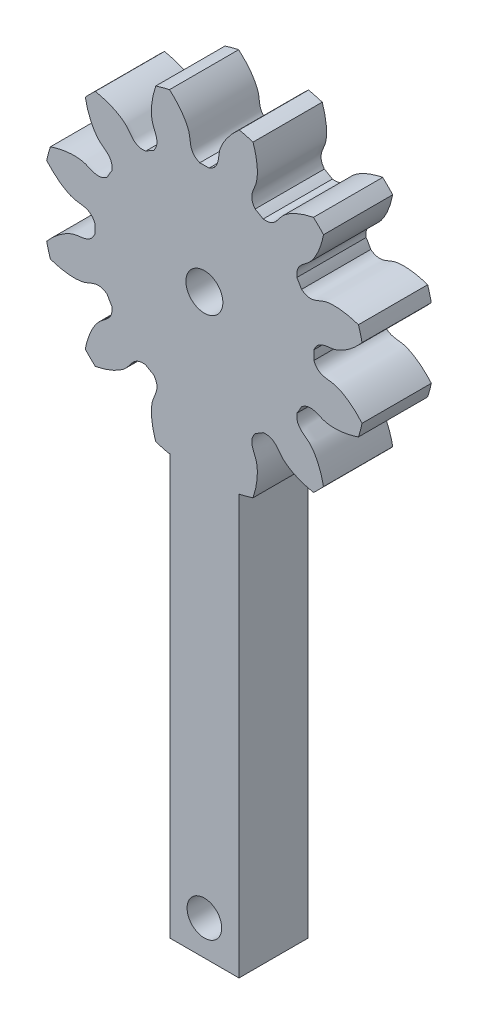
SolidWorks part; units mm, degrees
ref_plane "前视基准面" through (0, 0, 0) normal (0, 0, 1) x (1, 0, 0)
ref_plane "上视基准面" through (0, 0, 0) normal (0, 1, 0) x (1, 0, 0)
ref_plane "右视基准面" through (0, 0, 0) normal (1, 0, 0) x (0, 0, -1)
sketch "草图1" plane through (0, 0, 0) normal (0, 0, 1) x (1, 0, 0)
  circle A0 centre (0, 0) radius 14
extrude "凸台-拉伸1" add sketch "草图1" along normal blind 30
ref_axis "基准轴1" through (0, 0, -0.3001) along (0, 0, 1)
sketch "草图2" plane through (0, 0, 0) normal (0, 0, 1) x (1, 0, 0)
  line L0 (0, 0) -> (0, 14) construction
  circle A0 centre (0, 0) radius 14 construction
  arc A1 (0.4017, 9.4915) -> (-0.4017, 9.4915) centre (0, 0) ccw
  arc A2 (6.9952, 15.7899) -> (-6.9952, 15.7899) centre (0, 0) ccw
  spline S0 degree 3 poles (0.4017, 9.4915) (1.3616, 9.8986) (1.1487, 10.6896) (1.3523, 11.379) (1.3652, 11.4198) (1.3805, 11.4647) (1.3981, 11.5135) (1.4183, 11.5661) (1.4413, 11.6225) (1.4671, 11.6826) (1.4961, 11.7462) (1.5282, 11.8133) (1.5637, 11.8838) (1.6028, 11.9576) (1.6455, 12.0345) (1.6919, 12.1144) (1.7423, 12.1973) (1.7968, 12.2829) (1.8555, 12.3712) (1.9185, 12.462) (1.9859, 12.5552) (2.0579, 12.6506) (2.1346, 12.7481) (2.2161, 12.8475) (2.3025, 12.9487) (2.3939, 13.0516) (2.4904, 13.1559) (2.5921, 13.2615) (2.6991, 13.3682) (2.8114, 13.4759) (2.9292, 13.5844) (3.0525, 13.6935) (3.1814, 13.803) (3.316, 13.9128) (3.4563, 14.0226) (3.6023, 14.1323) (3.7542, 14.2418) (3.912, 14.3507) (4.0756, 14.4589) (4.2452, 14.5663) (4.4208, 14.6726) (4.6024, 14.7776) (4.79, 14.8811) (4.9836, 14.983) (5.1832, 15.083) (5.3889, 15.1809) (5.6006, 15.2765) (5.8183, 15.3697) (6.042, 15.4602) (6.2717, 15.5478) (6.5888, 15.6615) (6.8312, 15.7402) (6.9952, 15.7899) knots 0 0 0 0 0.218015 0.222044 0.226546 0.231522 0.236972 0.242897 0.249295 0.256167 0.263513 0.271332 0.279626 0.288394 0.297636 0.307351 0.317541 0.328204 0.339341 0.350953 0.363038 0.375597 0.38863 0.402137 0.416118 0.430573 0.445502 0.460904 0.476781 0.493132 0.509956 0.527255 0.545027 0.563273 0.581994 0.601188 0.620856 0.640998 0.661614 0.682704 0.704268 0.726305 0.748817 0.771803 0.795262 0.819196 0.843603 0.868484 0.89384 0.919669 0.945972 1 1 1 1
  spline S1 degree 3 poles (-0.4017, 9.4915) (-1.3616, 9.8986) (-1.1487, 10.6896) (-1.3523, 11.379) (-1.3652, 11.4198) (-1.3805, 11.4647) (-1.3981, 11.5135) (-1.4183, 11.5661) (-1.4413, 11.6225) (-1.4671, 11.6826) (-1.4961, 11.7462) (-1.5282, 11.8133) (-1.5637, 11.8838) (-1.6028, 11.9576) (-1.6455, 12.0345) (-1.6919, 12.1144) (-1.7423, 12.1973) (-1.7968, 12.2829) (-1.8555, 12.3712) (-1.9185, 12.462) (-1.9859, 12.5552) (-2.0579, 12.6506) (-2.1346, 12.7481) (-2.2161, 12.8475) (-2.3025, 12.9487) (-2.3939, 13.0516) (-2.4904, 13.1559) (-2.5921, 13.2615) (-2.6991, 13.3682) (-2.8114, 13.4759) (-2.9292, 13.5844) (-3.0525, 13.6935) (-3.1814, 13.803) (-3.316, 13.9128) (-3.4563, 14.0226) (-3.6023, 14.1323) (-3.7542, 14.2418) (-3.912, 14.3507) (-4.0756, 14.4589) (-4.2452, 14.5663) (-4.4208, 14.6726) (-4.6024, 14.7776) (-4.79, 14.8811) (-4.9836, 14.983) (-5.1832, 15.083) (-5.3889, 15.1809) (-5.6006, 15.2765) (-5.8183, 15.3697) (-6.042, 15.4602) (-6.2717, 15.5478) (-6.5888, 15.6615) (-6.8312, 15.7402) (-6.9952, 15.7899) knots 0 0 0 0 0.218015 0.222044 0.226546 0.231522 0.236972 0.242897 0.249295 0.256167 0.263513 0.271332 0.279626 0.288394 0.297636 0.307351 0.317541 0.328204 0.339341 0.350953 0.363038 0.375597 0.38863 0.402137 0.416118 0.430573 0.445502 0.460904 0.476781 0.493132 0.509956 0.527255 0.545027 0.563273 0.581994 0.601188 0.620856 0.640998 0.661614 0.682704 0.704268 0.726305 0.748817 0.771803 0.795262 0.819196 0.843603 0.868484 0.89384 0.919669 0.945972 1 1 1 1
extrude "切除-拉伸1" cut sketch "草图2" along normal through all
pattern_circular "阵列(圆周)1" count 12 every 30 about axis through (0, 0, -0.3001) along (0, 0, 1) of "切除-拉伸1"
sketch "草图3" plane through (0, 0, 0) normal (0, 0, 1) x (1, 0, 0)
  circle A0 centre (0, 0) radius 12 construction
  dimension "Dn" = 24
sketch "草图4" plane through (0, 0, 30) normal (0, 0, 1) x (1, 0, 0)
  arc A24 (-4.3979, 8.4207) -> (-5.0936, 8.019) centre (0, 0) ccw
  arc A25 (-9.4547, 10.3251) -> (-10.3251, 9.4547) centre (0, 0) ccw
  arc A26 (-8.019, 5.0936) -> (-8.4207, 4.3979) centre (0, 0) ccw
  arc A27 (-13.3506, 4.2145) -> (-13.6692, 3.0255) centre (0, 0) ccw
  arc A28 (-9.4915, 0.4017) -> (-9.4915, -0.4017) centre (0, 0) ccw
  arc A29 (-13.6692, -3.0255) -> (-13.3506, -4.2145) centre (0, 0) ccw
  arc A30 (-8.4207, -4.3979) -> (-8.019, -5.0936) centre (0, 0) ccw
  arc A31 (-10.3251, -9.4547) -> (-9.4547, -10.3251) centre (0, 0) ccw
  arc A32 (-5.0936, -8.019) -> (-4.3979, -8.4207) centre (0, 0) ccw
  arc A33 (-4.2145, -13.3506) -> (-3.0255, -13.6692) centre (0, 0) ccw
  arc A34 (-0.4017, -9.4915) -> (0.4017, -9.4915) centre (0, 0) ccw
  arc A35 (3.0255, -13.6692) -> (4.2145, -13.3506) centre (0, 0) ccw
  arc A36 (4.3979, -8.4207) -> (5.0936, -8.019) centre (0, 0) ccw
  arc A37 (9.4547, -10.3251) -> (10.3251, -9.4547) centre (0, 0) ccw
  arc A38 (8.019, -5.0936) -> (8.4207, -4.3979) centre (0, 0) ccw
  arc A39 (13.3506, -4.2145) -> (13.6692, -3.0255) centre (0, 0) ccw
  arc A40 (9.4915, -0.4017) -> (9.4915, 0.4017) centre (0, 0) ccw
  arc A41 (13.6692, 3.0255) -> (13.3506, 4.2145) centre (0, 0) ccw
  arc A42 (8.4207, 4.3979) -> (8.019, 5.0936) centre (0, 0) ccw
  arc A43 (10.3251, 9.4547) -> (9.4547, 10.3251) centre (0, 0) ccw
  arc A44 (5.0936, 8.019) -> (4.3979, 8.4207) centre (0, 0) ccw
  arc A45 (4.2145, 13.3506) -> (3.0255, 13.6692) centre (0, 0) ccw
  arc A46 (0.4017, 9.4915) -> (-0.4017, 9.4915) centre (0, 0) ccw
  arc A47 (-3.0255, 13.6692) -> (-4.2145, 13.3506) centre (0, 0) ccw
  arc A48 (-4.3979, 8.4207) -> (-5.0936, 8.019) centre (0, 0) ccw
  arc A49 (-9.4547, 10.3251) -> (-10.3251, 9.4547) centre (0, 0) ccw
  arc A50 (-8.019, 5.0936) -> (-8.4207, 4.3979) centre (0, 0) ccw
  arc A51 (-13.3506, 4.2145) -> (-13.6692, 3.0255) centre (0, 0) ccw
  arc A52 (-9.4915, 0.4017) -> (-9.4915, -0.4017) centre (0, 0) ccw
  arc A53 (-13.6692, -3.0255) -> (-13.3506, -4.2145) centre (0, 0) ccw
  arc A54 (-8.4207, -4.3979) -> (-8.019, -5.0936) centre (0, 0) ccw
  arc A55 (-10.3251, -9.4547) -> (-9.4547, -10.3251) centre (0, 0) ccw
  arc A56 (-5.0936, -8.019) -> (-4.3979, -8.4207) centre (0, 0) ccw
  arc A57 (-4.2145, -13.3506) -> (-3.0255, -13.6692) centre (0, 0) ccw
  arc A58 (-0.4017, -9.4915) -> (0.4017, -9.4915) centre (0, 0) ccw
  arc A59 (3.0255, -13.6692) -> (4.2145, -13.3506) centre (0, 0) ccw
  arc A60 (4.3979, -8.4207) -> (5.0936, -8.019) centre (0, 0) ccw
  arc A61 (9.4547, -10.3251) -> (10.3251, -9.4547) centre (0, 0) ccw
  arc A62 (8.019, -5.0936) -> (8.4207, -4.3979) centre (0, 0) ccw
  arc A63 (13.3506, -4.2145) -> (13.6692, -3.0255) centre (0, 0) ccw
  arc A64 (9.4915, -0.4017) -> (9.4915, 0.4017) centre (0, 0) ccw
  arc A65 (13.6692, 3.0255) -> (13.3506, 4.2145) centre (0, 0) ccw
  arc A66 (8.4207, 4.3979) -> (8.019, 5.0936) centre (0, 0) ccw
  arc A67 (10.3251, 9.4547) -> (9.4547, 10.3251) centre (0, 0) ccw
  arc A68 (5.0936, 8.019) -> (4.3979, 8.4207) centre (0, 0) ccw
  arc A69 (4.2145, 13.3506) -> (3.0255, 13.6692) centre (0, 0) ccw
  arc A70 (0.4017, 9.4915) -> (-0.4017, 9.4915) centre (0, 0) ccw
  arc A71 (-3.0255, 13.6692) -> (-4.2145, 13.3506) centre (0, 0) ccw
  spline S24 degree 3 poles (2052.1623, 2191.1493) (-39.4787, -48.9387) (-0.5786, 3.2069) (-6.8721, 9.1892) (-6.9309, 9.2418) (-7.0145, 9.3106) (-7.1151, 9.387) (-7.2335, 9.4697) (-7.3702, 9.5573) (-7.5259, 9.6485) (-7.7011, 9.7419) (-7.8961, 9.8361) (-8.1112, 9.9296) (-8.3468, 10.021) (-8.6028, 10.1087) (-8.8795, 10.1914) (-39.0749, 17.9093) (-111.0172, -152.8208) (2365.5035, 1842.2647) knots -2.028933 -2.028933 -2.028933 -2.028933 0.69442 0.698448 0.707927 0.719301 0.732571 0.747737 0.764798 0.783756 0.804608 0.827357 0.852001 0.878542 0.906977 0.937309 0.969536 10.7291 10.7291 10.7291 10.7291 only from (-5.0936, 8.019) to (-9.4547, 10.3251)
  spline S25 degree 3 poles (-1837.9661, -2368.8794) (150.6443, 113.0421) (-18.3423, 38.3111) (-10.1508, 8.7386) (-10.0654, 8.4722) (-9.9757, 8.2264) (-9.883, 8.0011) (-9.789, 7.7961) (-9.695, 7.6111) (-9.6025, 7.4457) (-9.5129, 7.2995) (-9.4276, 7.172) (-9.359, 7.0778) (-9.2968, 6.9977) (-9.2418, 6.9309) (-9.1892, 6.8721) (-3.2069, 0.5786) (48.9386, 39.4786) (-2191.1398, -2052.1534) knots -9.563336 -9.563336 -9.563336 -9.563336 0.046814 0.078094 0.107478 0.134965 0.160558 0.184254 0.206055 0.22596 0.243969 0.260083 0.274301 0.280699 0.292073 0.301552 0.30558 3.02893 3.02893 3.02893 3.02893 only from (-10.3251, 9.4547) to (-8.019, 5.0936)
  spline S26 degree 3 poles (681.6501, 2923.6721) (-9.7202, -62.1215) (-2.1045, 2.4879) (-10.546, 4.522) (-10.6233, 4.5381) (-10.7301, 4.556) (-10.8554, 4.5718) (-10.9992, 4.5842) (-11.1614, 4.5917) (-11.3419, 4.5929) (-11.5403, 4.5862) (-11.7563, 4.5702) (-11.9893, 4.5437) (-12.239, 4.505) (-12.5046, 4.453) (-12.7855, 4.3862) (-42.7945, -4.0276) (-19.7333, -187.8553) (1127.4538, 2778.1998) knots -2.028933 -2.028933 -2.028933 -2.028933 0.69442 0.698448 0.707927 0.719301 0.732571 0.747737 0.764798 0.783756 0.804608 0.827357 0.852001 0.878542 0.906977 0.937309 0.969536 10.7291 10.7291 10.7291 10.7291 only from (-8.4207, 4.3979) to (-13.3506, 4.2145)
  spline S27 degree 3 poles (-407.2856, -2970.4928) (73.9407, 173.2195) (-35.0405, 24.0073) (-13.1601, 2.4924) (-12.953, 2.3045) (-12.7524, 2.1365) (-12.5595, 1.9877) (-12.3755, 1.8571) (-12.2016, 1.7439) (-12.0389, 1.6469) (-11.8882, 1.5651) (-11.7506, 1.4973) (-11.6441, 1.4501) (-11.5501, 1.4118) (-11.4691, 1.3815) (-11.3941, 1.3568) (-3.0665, -1.1024) (22.6428, 58.6587) (-871.506, -2872.7869) knots -9.563336 -9.563336 -9.563336 -9.563336 0.046814 0.078094 0.107478 0.134965 0.160558 0.184254 0.206055 0.22596 0.243969 0.260083 0.274301 0.280699 0.292073 0.301552 0.30558 3.02893 3.02893 3.02893 3.02893 only from (-13.6692, 3.0255) to (-9.4915, 0.4017)
  spline S28 degree 3 poles (-871.5098, 2872.7993) (22.6429, -58.6589) (-3.0665, 1.1024) (-11.3941, -1.3568) (-11.4691, -1.3815) (-11.5705, -1.4194) (-11.687, -1.4684) (-11.8177, -1.5295) (-11.962, -1.6042) (-12.1188, -1.6934) (-12.2873, -1.7984) (-12.4663, -1.9202) (-12.6549, -2.0597) (-12.8518, -2.218) (-13.0558, -2.3959) (-13.2657, -2.5942) (-35.0474, -24.8852) (76.8381, -172.5541) (-412.6963, 2969.7185) knots -2.028933 -2.028933 -2.028933 -2.028933 0.69442 0.698448 0.707927 0.719301 0.732571 0.747737 0.764798 0.783756 0.804608 0.827357 0.852001 0.878542 0.906977 0.937309 0.969536 10.7291 10.7291 10.7291 10.7291 only from (-9.4915, -0.4017) to (-13.6692, -3.0255)
  spline S29 degree 3 poles (1132.5267, -2776.1651) (-22.5752, 186.9828) (-42.3496, 3.2707) (-12.6432, -4.4215) (-12.3699, -4.4808) (-12.1121, -4.5259) (-11.8707, -4.5584) (-11.6461, -4.5794) (-11.4389, -4.5906) (-11.2494, -4.5932) (-11.078, -4.5887) (-10.925, -4.5786) (-10.8091, -4.5662) (-10.7085, -4.5524) (-10.6233, -4.5381) (-10.546, -4.522) (-2.1045, -2.4879) (-9.7201, 62.1214) (681.6471, -2923.6594) knots -9.563336 -9.563336 -9.563336 -9.563336 0.046814 0.078094 0.107478 0.134965 0.160558 0.184254 0.206055 0.22596 0.243969 0.260083 0.274301 0.280699 0.292073 0.301552 0.30558 3.02893 3.02893 3.02893 3.02893 only from (-13.3506, -4.2145) to (-8.4207, -4.3979)
  spline S30 degree 3 poles (-2191.1493, 2052.1623) (48.9387, -39.4787) (-3.2069, -0.5786) (-9.1892, -6.8721) (-9.2418, -6.9309) (-9.3106, -7.0145) (-9.387, -7.1151) (-9.4697, -7.2335) (-9.5573, -7.3702) (-9.6485, -7.5259) (-9.7419, -7.7011) (-9.8361, -7.8961) (-9.9296, -8.1112) (-10.021, -8.3468) (-10.1087, -8.6028) (-10.1914, -8.8795) (-17.9093, -39.0749) (152.8208, -111.0172) (-1842.2647, 2365.5035) knots -2.028933 -2.028933 -2.028933 -2.028933 0.69442 0.698448 0.707927 0.719301 0.732571 0.747737 0.764798 0.783756 0.804608 0.827357 0.852001 0.878542 0.906977 0.937309 0.969536 10.7291 10.7291 10.7291 10.7291 only from (-8.019, -5.0936) to (-10.3251, -9.4547)
  spline S31 degree 3 poles (2368.8794, -1837.9661) (-113.0421, 150.6443) (-38.3111, -18.3423) (-8.7386, -10.1508) (-8.4722, -10.0654) (-8.2264, -9.9757) (-8.0011, -9.883) (-7.7961, -9.789) (-7.6111, -9.695) (-7.4457, -9.6025) (-7.2995, -9.5129) (-7.172, -9.4276) (-7.0778, -9.359) (-6.9977, -9.2968) (-6.9309, -9.2418) (-6.8721, -9.1892) (-0.5786, -3.2069) (-39.4786, 48.9386) (2052.1534, -2191.1398) knots -9.563336 -9.563336 -9.563336 -9.563336 0.046814 0.078094 0.107478 0.134965 0.160558 0.184254 0.206055 0.22596 0.243969 0.260083 0.274301 0.280699 0.292073 0.301552 0.30558 3.02893 3.02893 3.02893 3.02893 only from (-9.4547, -10.3251) to (-5.0936, -8.019)
  spline S32 degree 3 poles (-2923.6721, 681.6501) (62.1215, -9.7202) (-2.4879, -2.1045) (-4.522, -10.546) (-4.5381, -10.6233) (-4.556, -10.7301) (-4.5718, -10.8554) (-4.5842, -10.9992) (-4.5917, -11.1614) (-4.5929, -11.3419) (-4.5862, -11.5403) (-4.5702, -11.7563) (-4.5437, -11.9893) (-4.505, -12.239) (-4.453, -12.5046) (-4.3862, -12.7855) (4.0276, -42.7945) (187.8553, -19.7333) (-2778.1998, 1127.4538) knots -2.028933 -2.028933 -2.028933 -2.028933 0.69442 0.698448 0.707927 0.719301 0.732571 0.747737 0.764798 0.783756 0.804608 0.827357 0.852001 0.878542 0.906977 0.937309 0.969536 10.7291 10.7291 10.7291 10.7291 only from (-4.3979, -8.4207) to (-4.2145, -13.3506)
  spline S33 degree 3 poles (2970.4928, -407.2856) (-173.2195, 73.9407) (-24.0073, -35.0405) (-2.4924, -13.1601) (-2.3045, -12.953) (-2.1365, -12.7524) (-1.9877, -12.5595) (-1.8571, -12.3755) (-1.7439, -12.2016) (-1.6469, -12.0389) (-1.5651, -11.8882) (-1.4973, -11.7506) (-1.4501, -11.6441) (-1.4118, -11.5501) (-1.3815, -11.4691) (-1.3568, -11.3941) (1.1024, -3.0665) (-58.6587, 22.6428) (2872.7869, -871.506) knots -9.563336 -9.563336 -9.563336 -9.563336 0.046814 0.078094 0.107478 0.134965 0.160558 0.184254 0.206055 0.22596 0.243969 0.260083 0.274301 0.280699 0.292073 0.301552 0.30558 3.02893 3.02893 3.02893 3.02893 only from (-3.0255, -13.6692) to (-0.4017, -9.4915)
  spline S34 degree 3 poles (-2872.7993, -871.5098) (58.6589, 22.6429) (-1.1024, -3.0665) (1.3568, -11.3941) (1.3815, -11.4691) (1.4194, -11.5705) (1.4684, -11.687) (1.5295, -11.8177) (1.6042, -11.962) (1.6934, -12.1188) (1.7984, -12.2873) (1.9202, -12.4663) (2.0597, -12.6549) (2.218, -12.8518) (2.3959, -13.0558) (2.5942, -13.2657) (24.8852, -35.0474) (172.5541, 76.8381) (-2969.7185, -412.6963) knots -2.028933 -2.028933 -2.028933 -2.028933 0.69442 0.698448 0.707927 0.719301 0.732571 0.747737 0.764798 0.783756 0.804608 0.827357 0.852001 0.878542 0.906977 0.937309 0.969536 10.7291 10.7291 10.7291 10.7291 only from (0.4017, -9.4915) to (3.0255, -13.6692)
  spline S35 degree 3 poles (2776.1651, 1132.5267) (-186.9828, -22.5752) (-3.2707, -42.3496) (4.4215, -12.6432) (4.4808, -12.3699) (4.5259, -12.1121) (4.5584, -11.8707) (4.5794, -11.6461) (4.5906, -11.4389) (4.5932, -11.2494) (4.5887, -11.078) (4.5786, -10.925) (4.5662, -10.8091) (4.5524, -10.7085) (4.5381, -10.6233) (4.522, -10.546) (2.4879, -2.1045) (-62.1214, -9.7201) (2923.6594, 681.6471) knots -9.563336 -9.563336 -9.563336 -9.563336 0.046814 0.078094 0.107478 0.134965 0.160558 0.184254 0.206055 0.22596 0.243969 0.260083 0.274301 0.280699 0.292073 0.301552 0.30558 3.02893 3.02893 3.02893 3.02893 only from (4.2145, -13.3506) to (4.3979, -8.4207)
  spline S36 degree 3 poles (-2052.1623, -2191.1493) (39.4787, 48.9387) (0.5786, -3.2069) (6.8721, -9.1892) (6.9309, -9.2418) (7.0145, -9.3106) (7.1151, -9.387) (7.2335, -9.4697) (7.3702, -9.5573) (7.5259, -9.6485) (7.7011, -9.7419) (7.8961, -9.8361) (8.1112, -9.9296) (8.3468, -10.021) (8.6028, -10.1087) (8.8795, -10.1914) (39.0749, -17.9093) (111.0172, 152.8208) (-2365.5035, -1842.2647) knots -2.028933 -2.028933 -2.028933 -2.028933 0.69442 0.698448 0.707927 0.719301 0.732571 0.747737 0.764798 0.783756 0.804608 0.827357 0.852001 0.878542 0.906977 0.937309 0.969536 10.7291 10.7291 10.7291 10.7291 only from (5.0936, -8.019) to (9.4547, -10.3251)
  spline S37 degree 3 poles (1837.9661, 2368.8794) (-150.6443, -113.0421) (18.3423, -38.3111) (10.1508, -8.7386) (10.0654, -8.4722) (9.9757, -8.2264) (9.883, -8.0011) (9.789, -7.7961) (9.695, -7.6111) (9.6025, -7.4457) (9.5129, -7.2995) (9.4276, -7.172) (9.359, -7.0778) (9.2968, -6.9977) (9.2418, -6.9309) (9.1892, -6.8721) (3.2069, -0.5786) (-48.9386, -39.4786) (2191.1398, 2052.1534) knots -9.563336 -9.563336 -9.563336 -9.563336 0.046814 0.078094 0.107478 0.134965 0.160558 0.184254 0.206055 0.22596 0.243969 0.260083 0.274301 0.280699 0.292073 0.301552 0.30558 3.02893 3.02893 3.02893 3.02893 only from (10.3251, -9.4547) to (8.019, -5.0936)
  spline S38 degree 3 poles (-681.6501, -2923.6721) (9.7202, 62.1215) (2.1045, -2.4879) (10.546, -4.522) (10.6233, -4.5381) (10.7301, -4.556) (10.8554, -4.5718) (10.9992, -4.5842) (11.1614, -4.5917) (11.3419, -4.5929) (11.5403, -4.5862) (11.7563, -4.5702) (11.9893, -4.5437) (12.239, -4.505) (12.5046, -4.453) (12.7855, -4.3862) (42.7945, 4.0276) (19.7333, 187.8553) (-1127.4538, -2778.1998) knots -2.028933 -2.028933 -2.028933 -2.028933 0.69442 0.698448 0.707927 0.719301 0.732571 0.747737 0.764798 0.783756 0.804608 0.827357 0.852001 0.878542 0.906977 0.937309 0.969536 10.7291 10.7291 10.7291 10.7291 only from (8.4207, -4.3979) to (13.3506, -4.2145)
  spline S39 degree 3 poles (407.2856, 2970.4928) (-73.9407, -173.2195) (35.0405, -24.0073) (13.1601, -2.4924) (12.953, -2.3045) (12.7524, -2.1365) (12.5595, -1.9877) (12.3755, -1.8571) (12.2016, -1.7439) (12.0389, -1.6469) (11.8882, -1.5651) (11.7506, -1.4973) (11.6441, -1.4501) (11.5501, -1.4118) (11.4691, -1.3815) (11.3941, -1.3568) (3.0665, 1.1024) (-22.6428, -58.6587) (871.506, 2872.7869) knots -9.563336 -9.563336 -9.563336 -9.563336 0.046814 0.078094 0.107478 0.134965 0.160558 0.184254 0.206055 0.22596 0.243969 0.260083 0.274301 0.280699 0.292073 0.301552 0.30558 3.02893 3.02893 3.02893 3.02893 only from (13.6692, -3.0255) to (9.4915, -0.4017)
  spline S40 degree 3 poles (871.5098, -2872.7993) (-22.6429, 58.6589) (3.0665, -1.1024) (11.3941, 1.3568) (11.4691, 1.3815) (11.5705, 1.4194) (11.687, 1.4684) (11.8177, 1.5295) (11.962, 1.6042) (12.1188, 1.6934) (12.2873, 1.7984) (12.4663, 1.9202) (12.6549, 2.0597) (12.8518, 2.218) (13.0558, 2.3959) (13.2657, 2.5942) (35.0474, 24.8852) (-76.8381, 172.5541) (412.6963, -2969.7185) knots -2.028933 -2.028933 -2.028933 -2.028933 0.69442 0.698448 0.707927 0.719301 0.732571 0.747737 0.764798 0.783756 0.804608 0.827357 0.852001 0.878542 0.906977 0.937309 0.969536 10.7291 10.7291 10.7291 10.7291 only from (9.4915, 0.4017) to (13.6692, 3.0255)
  spline S41 degree 3 poles (-1132.5267, 2776.1651) (22.5752, -186.9828) (42.3496, -3.2707) (12.6432, 4.4215) (12.3699, 4.4808) (12.1121, 4.5259) (11.8707, 4.5584) (11.6461, 4.5794) (11.4389, 4.5906) (11.2494, 4.5932) (11.078, 4.5887) (10.925, 4.5786) (10.8091, 4.5662) (10.7085, 4.5524) (10.6233, 4.5381) (10.546, 4.522) (2.1045, 2.4879) (9.7201, -62.1214) (-681.6471, 2923.6594) knots -9.563336 -9.563336 -9.563336 -9.563336 0.046814 0.078094 0.107478 0.134965 0.160558 0.184254 0.206055 0.22596 0.243969 0.260083 0.274301 0.280699 0.292073 0.301552 0.30558 3.02893 3.02893 3.02893 3.02893 only from (13.3506, 4.2145) to (8.4207, 4.3979)
  spline S42 degree 3 poles (2191.1493, -2052.1623) (-48.9387, 39.4787) (3.2069, 0.5786) (9.1892, 6.8721) (9.2418, 6.9309) (9.3106, 7.0145) (9.387, 7.1151) (9.4697, 7.2335) (9.5573, 7.3702) (9.6485, 7.5259) (9.7419, 7.7011) (9.8361, 7.8961) (9.9296, 8.1112) (10.021, 8.3468) (10.1087, 8.6028) (10.1914, 8.8795) (17.9093, 39.0749) (-152.8208, 111.0172) (1842.2647, -2365.5035) knots -2.028933 -2.028933 -2.028933 -2.028933 0.69442 0.698448 0.707927 0.719301 0.732571 0.747737 0.764798 0.783756 0.804608 0.827357 0.852001 0.878542 0.906977 0.937309 0.969536 10.7291 10.7291 10.7291 10.7291 only from (8.019, 5.0936) to (10.3251, 9.4547)
  spline S43 degree 3 poles (-2368.8794, 1837.9661) (113.0421, -150.6443) (38.3111, 18.3423) (8.7386, 10.1508) (8.4722, 10.0654) (8.2264, 9.9757) (8.0011, 9.883) (7.7961, 9.789) (7.6111, 9.695) (7.4457, 9.6025) (7.2995, 9.5129) (7.172, 9.4276) (7.0778, 9.359) (6.9977, 9.2968) (6.9309, 9.2418) (6.8721, 9.1892) (0.5786, 3.2069) (39.4786, -48.9386) (-2052.1534, 2191.1398) knots -9.563336 -9.563336 -9.563336 -9.563336 0.046814 0.078094 0.107478 0.134965 0.160558 0.184254 0.206055 0.22596 0.243969 0.260083 0.274301 0.280699 0.292073 0.301552 0.30558 3.02893 3.02893 3.02893 3.02893 only from (9.4547, 10.3251) to (5.0936, 8.019)
  spline S44 degree 3 poles (2923.6721, -681.6501) (-62.1215, 9.7202) (2.4879, 2.1045) (4.522, 10.546) (4.5381, 10.6233) (4.556, 10.7301) (4.5718, 10.8554) (4.5842, 10.9992) (4.5917, 11.1614) (4.5929, 11.3419) (4.5862, 11.5403) (4.5702, 11.7563) (4.5437, 11.9893) (4.505, 12.239) (4.453, 12.5046) (4.3862, 12.7855) (-4.0276, 42.7945) (-187.8553, 19.7333) (2778.1998, -1127.4538) knots -2.028933 -2.028933 -2.028933 -2.028933 0.69442 0.698448 0.707927 0.719301 0.732571 0.747737 0.764798 0.783756 0.804608 0.827357 0.852001 0.878542 0.906977 0.937309 0.969536 10.7291 10.7291 10.7291 10.7291 only from (4.3979, 8.4207) to (4.2145, 13.3506)
  spline S45 degree 3 poles (-2970.4928, 407.2856) (173.2195, -73.9407) (24.0073, 35.0405) (2.4924, 13.1601) (2.3045, 12.953) (2.1365, 12.7524) (1.9877, 12.5595) (1.8571, 12.3755) (1.7439, 12.2016) (1.6469, 12.0389) (1.5651, 11.8882) (1.4973, 11.7506) (1.4501, 11.6441) (1.4118, 11.5501) (1.3815, 11.4691) (1.3568, 11.3941) (-1.1024, 3.0665) (58.6587, -22.6428) (-2872.7869, 871.506) knots -9.563336 -9.563336 -9.563336 -9.563336 0.046814 0.078094 0.107478 0.134965 0.160558 0.184254 0.206055 0.22596 0.243969 0.260083 0.274301 0.280699 0.292073 0.301552 0.30558 3.02893 3.02893 3.02893 3.02893 only from (3.0255, 13.6692) to (0.4017, 9.4915)
  spline S46 degree 3 poles (2872.7993, 871.5098) (-58.6589, -22.6429) (1.1024, 3.0665) (-1.3568, 11.3941) (-1.3815, 11.4691) (-1.4194, 11.5705) (-1.4684, 11.687) (-1.5295, 11.8177) (-1.6042, 11.962) (-1.6934, 12.1188) (-1.7984, 12.2873) (-1.9202, 12.4663) (-2.0597, 12.6549) (-2.218, 12.8518) (-2.3959, 13.0558) (-2.5942, 13.2657) (-24.8852, 35.0474) (-172.5541, -76.8381) (2969.7185, 412.6963) knots -2.028933 -2.028933 -2.028933 -2.028933 0.69442 0.698448 0.707927 0.719301 0.732571 0.747737 0.764798 0.783756 0.804608 0.827357 0.852001 0.878542 0.906977 0.937309 0.969536 10.7291 10.7291 10.7291 10.7291 only from (-0.4017, 9.4915) to (-3.0255, 13.6692)
  spline S47 degree 3 poles (-2776.1651, -1132.5267) (186.9828, 22.5752) (3.2707, 42.3496) (-4.4215, 12.6432) (-4.4808, 12.3699) (-4.5259, 12.1121) (-4.5584, 11.8707) (-4.5794, 11.6461) (-4.5906, 11.4389) (-4.5932, 11.2494) (-4.5887, 11.078) (-4.5786, 10.925) (-4.5662, 10.8091) (-4.5524, 10.7085) (-4.5381, 10.6233) (-4.522, 10.546) (-2.4879, 2.1045) (62.1214, 9.7201) (-2923.6594, -681.6471) knots -9.563336 -9.563336 -9.563336 -9.563336 0.046814 0.078094 0.107478 0.134965 0.160558 0.184254 0.206055 0.22596 0.243969 0.260083 0.274301 0.280699 0.292073 0.301552 0.30558 3.02893 3.02893 3.02893 3.02893 only from (-4.2145, 13.3506) to (-4.3979, 8.4207)
  spline S48 degree 3 poles (-5.0936, 8.019) (-6.1285, 7.8917) (-6.3397, 8.6831) (-6.8721, 9.1892) (-6.9309, 9.2418) (-7.0145, 9.3106) (-7.1151, 9.387) (-7.2335, 9.4697) (-7.3702, 9.5573) (-7.5259, 9.6485) (-7.7011, 9.7419) (-7.8961, 9.8361) (-8.1112, 9.9296) (-8.3468, 10.021) (-8.6028, 10.1087) (-8.8795, 10.1914) (-9.1655, 10.2645) (-9.3599, 10.3064) (-9.4547, 10.3251) knots 0.476404 0.476404 0.476404 0.476404 0.69442 0.698448 0.707927 0.719301 0.732571 0.747737 0.764798 0.783756 0.804608 0.827357 0.852001 0.878542 0.906977 0.937309 0.969536 1 1 1 1
  spline S49 degree 3 poles (-10.3251, 9.4547) (-10.2963, 9.309) (-10.2418, 9.0672) (-10.1508, 8.7386) (-10.0654, 8.4722) (-9.9757, 8.2264) (-9.883, 8.0011) (-9.789, 7.7961) (-9.695, 7.6111) (-9.6025, 7.4457) (-9.5129, 7.2995) (-9.4276, 7.172) (-9.359, 7.0778) (-9.2968, 6.9977) (-9.2418, 6.9309) (-9.1892, 6.8721) (-8.6831, 6.3397) (-7.8917, 6.1285) (-8.019, 5.0936) knots 0 0 0 0 0.046814 0.078094 0.107478 0.134965 0.160558 0.184254 0.206055 0.22596 0.243969 0.260083 0.274301 0.280699 0.292073 0.301552 0.30558 0.523596 0.523596 0.523596 0.523596
  spline S50 degree 3 poles (-8.4207, 4.3979) (-9.2532, 3.7701) (-9.8319, 4.35) (-10.546, 4.522) (-10.6233, 4.5381) (-10.7301, 4.556) (-10.8554, 4.5718) (-10.9992, 4.5842) (-11.1614, 4.5917) (-11.3419, 4.5929) (-11.5403, 4.5862) (-11.7563, 4.5702) (-11.9893, 4.5437) (-12.239, 4.505) (-12.5046, 4.453) (-12.7855, 4.3862) (-13.0698, 4.3065) (-13.2591, 4.2457) (-13.3506, 4.2145) knots 0.476404 0.476404 0.476404 0.476404 0.69442 0.698448 0.707927 0.719301 0.732571 0.747737 0.764798 0.783756 0.804608 0.827357 0.852001 0.878542 0.906977 0.937309 0.969536 1 1 1 1
  spline S51 degree 3 poles (-13.6692, 3.0255) (-13.5714, 2.9137) (-13.4033, 2.7316) (-13.1601, 2.4924) (-12.953, 2.3045) (-12.7524, 2.1365) (-12.5595, 1.9877) (-12.3755, 1.8571) (-12.2016, 1.7439) (-12.0389, 1.6469) (-11.8882, 1.5651) (-11.7506, 1.4973) (-11.6441, 1.4501) (-11.5501, 1.4118) (-11.4691, 1.3815) (-11.3941, 1.3568) (-10.6896, 1.1487) (-9.8986, 1.3616) (-9.4915, 0.4017) knots 0 0 0 0 0.046814 0.078094 0.107478 0.134965 0.160558 0.184254 0.206055 0.22596 0.243969 0.260083 0.274301 0.280699 0.292073 0.301552 0.30558 0.523596 0.523596 0.523596 0.523596
  spline S52 degree 3 poles (-9.4915, -0.4017) (-9.8986, -1.3616) (-10.6896, -1.1487) (-11.3941, -1.3568) (-11.4691, -1.3815) (-11.5705, -1.4194) (-11.687, -1.4684) (-11.8177, -1.5295) (-11.962, -1.6042) (-12.1188, -1.6934) (-12.2873, -1.7984) (-12.4663, -1.9202) (-12.6549, -2.0597) (-12.8518, -2.218) (-13.0558, -2.3959) (-13.2657, -2.5942) (-13.472, -2.8053) (-13.6056, -2.9527) (-13.6692, -3.0255) knots 0.476404 0.476404 0.476404 0.476404 0.69442 0.698448 0.707927 0.719301 0.732571 0.747737 0.764798 0.783756 0.804608 0.827357 0.852001 0.878542 0.906977 0.937309 0.969536 1 1 1 1
  spline S53 degree 3 poles (-13.3506, -4.2145) (-13.21, -4.2624) (-12.9734, -4.3361) (-12.6432, -4.4215) (-12.3699, -4.4808) (-12.1121, -4.5259) (-11.8707, -4.5584) (-11.6461, -4.5794) (-11.4389, -4.5906) (-11.2494, -4.5932) (-11.078, -4.5887) (-10.925, -4.5786) (-10.8091, -4.5662) (-10.7085, -4.5524) (-10.6233, -4.5381) (-10.546, -4.522) (-9.8319, -4.35) (-9.2532, -3.7701) (-8.4207, -4.3979) knots 0 0 0 0 0.046814 0.078094 0.107478 0.134965 0.160558 0.184254 0.206055 0.22596 0.243969 0.260083 0.274301 0.280699 0.292073 0.301552 0.30558 0.523596 0.523596 0.523596 0.523596
  spline S54 degree 3 poles (-8.019, -5.0936) (-7.8917, -6.1285) (-8.6831, -6.3397) (-9.1892, -6.8721) (-9.2418, -6.9309) (-9.3106, -7.0145) (-9.387, -7.1151) (-9.4697, -7.2335) (-9.5573, -7.3702) (-9.6485, -7.5259) (-9.7419, -7.7011) (-9.8361, -7.8961) (-9.9296, -8.1112) (-10.021, -8.3468) (-10.1087, -8.6028) (-10.1914, -8.8795) (-10.2645, -9.1655) (-10.3064, -9.3599) (-10.3251, -9.4547) knots 0.476404 0.476404 0.476404 0.476404 0.69442 0.698448 0.707927 0.719301 0.732571 0.747737 0.764798 0.783756 0.804608 0.827357 0.852001 0.878542 0.906977 0.937309 0.969536 1 1 1 1
  spline S55 degree 3 poles (-9.4547, -10.3251) (-9.309, -10.2963) (-9.0672, -10.2418) (-8.7386, -10.1508) (-8.4722, -10.0654) (-8.2264, -9.9757) (-8.0011, -9.883) (-7.7961, -9.789) (-7.6111, -9.695) (-7.4457, -9.6025) (-7.2995, -9.5129) (-7.172, -9.4276) (-7.0778, -9.359) (-6.9977, -9.2968) (-6.9309, -9.2418) (-6.8721, -9.1892) (-6.3397, -8.6831) (-6.1285, -7.8917) (-5.0936, -8.019) knots 0 0 0 0 0.046814 0.078094 0.107478 0.134965 0.160558 0.184254 0.206055 0.22596 0.243969 0.260083 0.274301 0.280699 0.292073 0.301552 0.30558 0.523596 0.523596 0.523596 0.523596
  spline S56 degree 3 poles (-4.3979, -8.4207) (-3.7701, -9.2532) (-4.35, -9.8319) (-4.522, -10.546) (-4.5381, -10.6233) (-4.556, -10.7301) (-4.5718, -10.8554) (-4.5842, -10.9992) (-4.5917, -11.1614) (-4.5929, -11.3419) (-4.5862, -11.5403) (-4.5702, -11.7563) (-4.5437, -11.9893) (-4.505, -12.239) (-4.453, -12.5046) (-4.3862, -12.7855) (-4.3065, -13.0698) (-4.2457, -13.2591) (-4.2145, -13.3506) knots 0.476404 0.476404 0.476404 0.476404 0.69442 0.698448 0.707927 0.719301 0.732571 0.747737 0.764798 0.783756 0.804608 0.827357 0.852001 0.878542 0.906977 0.937309 0.969536 1 1 1 1
  spline S57 degree 3 poles (-3.0255, -13.6692) (-2.9137, -13.5714) (-2.7316, -13.4033) (-2.4924, -13.1601) (-2.3045, -12.953) (-2.1365, -12.7524) (-1.9877, -12.5595) (-1.8571, -12.3755) (-1.7439, -12.2016) (-1.6469, -12.0389) (-1.5651, -11.8882) (-1.4973, -11.7506) (-1.4501, -11.6441) (-1.4118, -11.5501) (-1.3815, -11.4691) (-1.3568, -11.3941) (-1.1487, -10.6896) (-1.3616, -9.8986) (-0.4017, -9.4915) knots 0 0 0 0 0.046814 0.078094 0.107478 0.134965 0.160558 0.184254 0.206055 0.22596 0.243969 0.260083 0.274301 0.280699 0.292073 0.301552 0.30558 0.523596 0.523596 0.523596 0.523596
  spline S58 degree 3 poles (0.4017, -9.4915) (1.3616, -9.8986) (1.1487, -10.6896) (1.3568, -11.3941) (1.3815, -11.4691) (1.4194, -11.5705) (1.4684, -11.687) (1.5295, -11.8177) (1.6042, -11.962) (1.6934, -12.1188) (1.7984, -12.2873) (1.9202, -12.4663) (2.0597, -12.6549) (2.218, -12.8518) (2.3959, -13.0558) (2.5942, -13.2657) (2.8053, -13.472) (2.9527, -13.6056) (3.0255, -13.6692) knots 0.476404 0.476404 0.476404 0.476404 0.69442 0.698448 0.707927 0.719301 0.732571 0.747737 0.764798 0.783756 0.804608 0.827357 0.852001 0.878542 0.906977 0.937309 0.969536 1 1 1 1
  spline S59 degree 3 poles (4.2145, -13.3506) (4.2624, -13.21) (4.3361, -12.9734) (4.4215, -12.6432) (4.4808, -12.3699) (4.5259, -12.1121) (4.5584, -11.8707) (4.5794, -11.6461) (4.5906, -11.4389) (4.5932, -11.2494) (4.5887, -11.078) (4.5786, -10.925) (4.5662, -10.8091) (4.5524, -10.7085) (4.5381, -10.6233) (4.522, -10.546) (4.35, -9.8319) (3.7701, -9.2532) (4.3979, -8.4207) knots 0 0 0 0 0.046814 0.078094 0.107478 0.134965 0.160558 0.184254 0.206055 0.22596 0.243969 0.260083 0.274301 0.280699 0.292073 0.301552 0.30558 0.523596 0.523596 0.523596 0.523596
  spline S60 degree 3 poles (5.0936, -8.019) (6.1285, -7.8917) (6.3397, -8.6831) (6.8721, -9.1892) (6.9309, -9.2418) (7.0145, -9.3106) (7.1151, -9.387) (7.2335, -9.4697) (7.3702, -9.5573) (7.5259, -9.6485) (7.7011, -9.7419) (7.8961, -9.8361) (8.1112, -9.9296) (8.3468, -10.021) (8.6028, -10.1087) (8.8795, -10.1914) (9.1655, -10.2645) (9.3599, -10.3064) (9.4547, -10.3251) knots 0.476404 0.476404 0.476404 0.476404 0.69442 0.698448 0.707927 0.719301 0.732571 0.747737 0.764798 0.783756 0.804608 0.827357 0.852001 0.878542 0.906977 0.937309 0.969536 1 1 1 1
  spline S61 degree 3 poles (10.3251, -9.4547) (10.2963, -9.309) (10.2418, -9.0672) (10.1508, -8.7386) (10.0654, -8.4722) (9.9757, -8.2264) (9.883, -8.0011) (9.789, -7.7961) (9.695, -7.6111) (9.6025, -7.4457) (9.5129, -7.2995) (9.4276, -7.172) (9.359, -7.0778) (9.2968, -6.9977) (9.2418, -6.9309) (9.1892, -6.8721) (8.6831, -6.3397) (7.8917, -6.1285) (8.019, -5.0936) knots 0 0 0 0 0.046814 0.078094 0.107478 0.134965 0.160558 0.184254 0.206055 0.22596 0.243969 0.260083 0.274301 0.280699 0.292073 0.301552 0.30558 0.523596 0.523596 0.523596 0.523596
  spline S62 degree 3 poles (8.4207, -4.3979) (9.2532, -3.7701) (9.8319, -4.35) (10.546, -4.522) (10.6233, -4.5381) (10.7301, -4.556) (10.8554, -4.5718) (10.9992, -4.5842) (11.1614, -4.5917) (11.3419, -4.5929) (11.5403, -4.5862) (11.7563, -4.5702) (11.9893, -4.5437) (12.239, -4.505) (12.5046, -4.453) (12.7855, -4.3862) (13.0698, -4.3065) (13.2591, -4.2457) (13.3506, -4.2145) knots 0.476404 0.476404 0.476404 0.476404 0.69442 0.698448 0.707927 0.719301 0.732571 0.747737 0.764798 0.783756 0.804608 0.827357 0.852001 0.878542 0.906977 0.937309 0.969536 1 1 1 1
  spline S63 degree 3 poles (13.6692, -3.0255) (13.5714, -2.9137) (13.4033, -2.7316) (13.1601, -2.4924) (12.953, -2.3045) (12.7524, -2.1365) (12.5595, -1.9877) (12.3755, -1.8571) (12.2016, -1.7439) (12.0389, -1.6469) (11.8882, -1.5651) (11.7506, -1.4973) (11.6441, -1.4501) (11.5501, -1.4118) (11.4691, -1.3815) (11.3941, -1.3568) (10.6896, -1.1487) (9.8986, -1.3616) (9.4915, -0.4017) knots 0 0 0 0 0.046814 0.078094 0.107478 0.134965 0.160558 0.184254 0.206055 0.22596 0.243969 0.260083 0.274301 0.280699 0.292073 0.301552 0.30558 0.523596 0.523596 0.523596 0.523596
  spline S64 degree 3 poles (9.4915, 0.4017) (9.8986, 1.3616) (10.6896, 1.1487) (11.3941, 1.3568) (11.4691, 1.3815) (11.5705, 1.4194) (11.687, 1.4684) (11.8177, 1.5295) (11.962, 1.6042) (12.1188, 1.6934) (12.2873, 1.7984) (12.4663, 1.9202) (12.6549, 2.0597) (12.8518, 2.218) (13.0558, 2.3959) (13.2657, 2.5942) (13.472, 2.8053) (13.6056, 2.9527) (13.6692, 3.0255) knots 0.476404 0.476404 0.476404 0.476404 0.69442 0.698448 0.707927 0.719301 0.732571 0.747737 0.764798 0.783756 0.804608 0.827357 0.852001 0.878542 0.906977 0.937309 0.969536 1 1 1 1
  spline S65 degree 3 poles (13.3506, 4.2145) (13.21, 4.2624) (12.9734, 4.3361) (12.6432, 4.4215) (12.3699, 4.4808) (12.1121, 4.5259) (11.8707, 4.5584) (11.6461, 4.5794) (11.4389, 4.5906) (11.2494, 4.5932) (11.078, 4.5887) (10.925, 4.5786) (10.8091, 4.5662) (10.7085, 4.5524) (10.6233, 4.5381) (10.546, 4.522) (9.8319, 4.35) (9.2532, 3.7701) (8.4207, 4.3979) knots 0 0 0 0 0.046814 0.078094 0.107478 0.134965 0.160558 0.184254 0.206055 0.22596 0.243969 0.260083 0.274301 0.280699 0.292073 0.301552 0.30558 0.523596 0.523596 0.523596 0.523596
  spline S66 degree 3 poles (8.019, 5.0936) (7.8917, 6.1285) (8.6831, 6.3397) (9.1892, 6.8721) (9.2418, 6.9309) (9.3106, 7.0145) (9.387, 7.1151) (9.4697, 7.2335) (9.5573, 7.3702) (9.6485, 7.5259) (9.7419, 7.7011) (9.8361, 7.8961) (9.9296, 8.1112) (10.021, 8.3468) (10.1087, 8.6028) (10.1914, 8.8795) (10.2645, 9.1655) (10.3064, 9.3599) (10.3251, 9.4547) knots 0.476404 0.476404 0.476404 0.476404 0.69442 0.698448 0.707927 0.719301 0.732571 0.747737 0.764798 0.783756 0.804608 0.827357 0.852001 0.878542 0.906977 0.937309 0.969536 1 1 1 1
  spline S67 degree 3 poles (9.4547, 10.3251) (9.309, 10.2963) (9.0672, 10.2418) (8.7386, 10.1508) (8.4722, 10.0654) (8.2264, 9.9757) (8.0011, 9.883) (7.7961, 9.789) (7.6111, 9.695) (7.4457, 9.6025) (7.2995, 9.5129) (7.172, 9.4276) (7.0778, 9.359) (6.9977, 9.2968) (6.9309, 9.2418) (6.8721, 9.1892) (6.3397, 8.6831) (6.1285, 7.8917) (5.0936, 8.019) knots 0 0 0 0 0.046814 0.078094 0.107478 0.134965 0.160558 0.184254 0.206055 0.22596 0.243969 0.260083 0.274301 0.280699 0.292073 0.301552 0.30558 0.523596 0.523596 0.523596 0.523596
  spline S68 degree 3 poles (4.3979, 8.4207) (3.7701, 9.2532) (4.35, 9.8319) (4.522, 10.546) (4.5381, 10.6233) (4.556, 10.7301) (4.5718, 10.8554) (4.5842, 10.9992) (4.5917, 11.1614) (4.5929, 11.3419) (4.5862, 11.5403) (4.5702, 11.7563) (4.5437, 11.9893) (4.505, 12.239) (4.453, 12.5046) (4.3862, 12.7855) (4.3065, 13.0698) (4.2457, 13.2591) (4.2145, 13.3506) knots 0.476404 0.476404 0.476404 0.476404 0.69442 0.698448 0.707927 0.719301 0.732571 0.747737 0.764798 0.783756 0.804608 0.827357 0.852001 0.878542 0.906977 0.937309 0.969536 1 1 1 1
  spline S69 degree 3 poles (3.0255, 13.6692) (2.9137, 13.5714) (2.7316, 13.4033) (2.4924, 13.1601) (2.3045, 12.953) (2.1365, 12.7524) (1.9877, 12.5595) (1.8571, 12.3755) (1.7439, 12.2016) (1.6469, 12.0389) (1.5651, 11.8882) (1.4973, 11.7506) (1.4501, 11.6441) (1.4118, 11.5501) (1.3815, 11.4691) (1.3568, 11.3941) (1.1487, 10.6896) (1.3616, 9.8986) (0.4017, 9.4915) knots 0 0 0 0 0.046814 0.078094 0.107478 0.134965 0.160558 0.184254 0.206055 0.22596 0.243969 0.260083 0.274301 0.280699 0.292073 0.301552 0.30558 0.523596 0.523596 0.523596 0.523596
  spline S70 degree 3 poles (-0.4017, 9.4915) (-1.3616, 9.8986) (-1.1487, 10.6896) (-1.3568, 11.3941) (-1.3815, 11.4691) (-1.4194, 11.5705) (-1.4684, 11.687) (-1.5295, 11.8177) (-1.6042, 11.962) (-1.6934, 12.1188) (-1.7984, 12.2873) (-1.9202, 12.4663) (-2.0597, 12.6549) (-2.218, 12.8518) (-2.3959, 13.0558) (-2.5942, 13.2657) (-2.8053, 13.472) (-2.9527, 13.6056) (-3.0255, 13.6692) knots 0.476404 0.476404 0.476404 0.476404 0.69442 0.698448 0.707927 0.719301 0.732571 0.747737 0.764798 0.783756 0.804608 0.827357 0.852001 0.878542 0.906977 0.937309 0.969536 1 1 1 1
  spline S71 degree 3 poles (-4.2145, 13.3506) (-4.2624, 13.21) (-4.3361, 12.9734) (-4.4215, 12.6432) (-4.4808, 12.3699) (-4.5259, 12.1121) (-4.5584, 11.8707) (-4.5794, 11.6461) (-4.5906, 11.4389) (-4.5932, 11.2494) (-4.5887, 11.078) (-4.5786, 10.925) (-4.5662, 10.8091) (-4.5524, 10.7085) (-4.5381, 10.6233) (-4.522, 10.546) (-4.35, 9.8319) (-3.7701, 9.2532) (-4.3979, 8.4207) knots 0 0 0 0 0.046814 0.078094 0.107478 0.134965 0.160558 0.184254 0.206055 0.22596 0.243969 0.260083 0.274301 0.280699 0.292073 0.301552 0.30558 0.523596 0.523596 0.523596 0.523596
  dimension "D1" = 0
extrude "切除-拉伸2" cut sketch "草图4" against normal blind 24
sketch "草图5" plane through (0, 0, 6) normal (0, 0, 1) x (1, 0, 0)
  line L0 (0, 0) -> (0, -9.5) construction
  line L1 (3, -5) -> (-3, -5) construction
  line L2 (-3, -5) -> (-3, -50) construction
  line L3 (-3, -50) -> (3, -50) construction
  line L4 (3, -5) -> (3, -50) construction
  line L5 (0, -5) -> (-3, -5)
  line L6 (-3, -5) -> (-3, -50)
  line L7 (-3, -50) -> (3, -50)
  line L8 (3, -50) -> (3, -5)
  line L9 (3, -5) -> (0, -5)
  arc A1 (-0.4017, -9.4915) -> (0.4017, -9.4915) centre (0, 0) ccw construction
  point P12 (0, -50)
  point P13 (0, -5)
  dimension "D2" = 5
  dimension "D3" = 45
  dimension "D4" = 3
extrude "凸台-拉伸2" add sketch "草图5" against normal blind 6
sketch "草图6" plane through (0, 0, 6) normal (0, 0, 1) x (1, 0, 0)
  circle A0 centre (0, 0) radius 1.6
  dimension "D1" = 3.2
extrude "切除-拉伸3" cut sketch "草图6" against normal blind 6
sketch "草图7" plane through (0, 0, 6) normal (0, 0, 1) x (1, 0, 0)
  line L0 (0, -50) -> (0, -47) construction
  line L1 (-3, -50) -> (3, -50) construction
  circle A0 centre (0, -47) radius 1.5
  dimension "D1" = 3
  dimension "D2" = 3
extrude "切除-拉伸4" cut sketch "草图7" against normal blind 6
